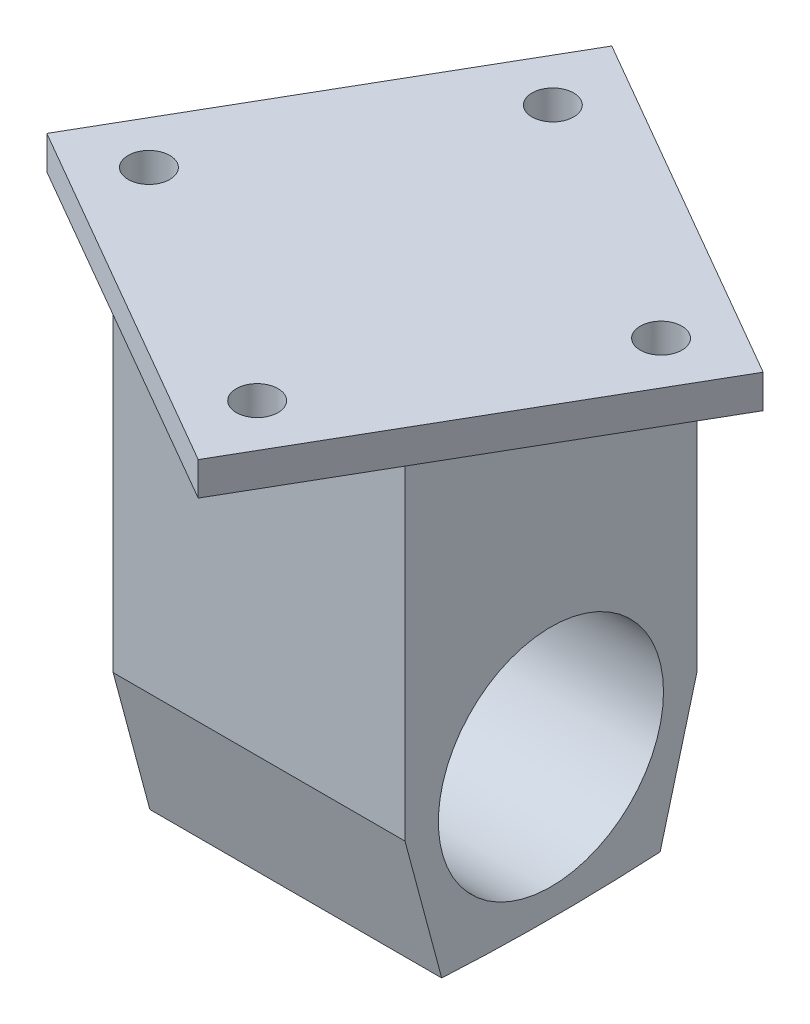
SolidWorks part; units mm, degrees
material "ABS"
ref_plane "Front Plane" through (0, 0, 0) normal (0, 0, 1) x (1, 0, 0)
ref_plane "Top Plane" through (0, 0, 0) normal (0, 1, 0) x (1, 0, 0)
ref_plane "Right Plane" through (0, 0, 0) normal (1, 0, 0) x (0, 0, -1)
sketch "Sketch1" plane through (0, 0, 0) normal (0, 1, 0) x (1, 0, 0)
  line L1 (-22.225, -22.225) -> (22.225, -22.225)
  line L2 (-22.225, -22.225) -> (-22.225, 22.225)
  line L3 (-22.225, 22.225) -> (22.225, 22.225)
  line L4 (22.225, -22.225) -> (22.225, 22.225)
  line L5 (-22.225, -22.225) -> (22.225, 22.225) construction
  line L6 (-22.225, 22.225) -> (22.225, -22.225) construction
  point P0 (0, 0)
extrude "Boss-Extrude1" add sketch "Sketch1" along normal blind 50.292
sketch "Sketch2" plane through (22.225, 0, 0) normal (1, 0, 0) x (0, 0, -1)
  line L0 (-22.225, 0) -> (-16.6371, -20.8543)
  line L1 (22.225, 0) -> (16.6371, -20.8543)
  line L2 (-22.225, 0) -> (22.225, 0)
  line L3 (-22.225, 0) -> (22.225, 0) construction
  arc A1 (16.6371, -20.8543) -> (-16.6371, -20.8543) centre (0, 278.6719) cw
  dimension "D1" = 21.59
  dimension "D2" = 21.59
  dimension "D3" = 75
  dimension "D4" = 75
extrude "Boss-Extrude2" add sketch "Sketch2" against normal up to vertex (44.45 mm away) contours L0 A1 L1 L2 up to point (-22.225, 0, -22.225)
sketch "Sketch3" plane through (22.225, 0, 0) normal (1, 0, 0) x (0, 0, -1)
  circle A0 centre (0, 0) radius 17.145
extrude "Cut-Extrude1" cut sketch "Sketch3" against normal blind 127 contours A0
sketch "Sketch4" plane through (0, 50.292, 0) normal (0, 1, 0) x (1, 0, 0)
  line L0 (-46.8473, -12.5527) -> (46.8473, 12.5527) construction
  line L5 (13.6389, -50.901) -> (-13.6389, 50.901) construction
  line L6 (43.0243, 11.5283) -> (11.5283, -43.0243)
  line L11 (11.5283, -43.0243) -> (-43.0243, -11.5283)
  line L12 (-43.0243, -11.5283) -> (-11.5283, 43.0243)
  line L13 (-11.5283, 43.0243) -> (43.0243, 11.5283)
  line L14 (11.5283, -43.0243) -> (-11.5283, 43.0243) construction
  line L15 (-43.0243, -11.5283) -> (43.0243, 11.5283) construction
  point P1 (0, 0)
  point P4 (0, 0)
  point P11 (0, 0)
  dimension "D1" = 62.992
  dimension "D2" = 62.992
  dimension "D3" = 0
  dimension "D4" = 0
extrude "Boss-Extrude3" add sketch "Sketch4" along normal blind 5.08
sketch "Sketch5" plane through (0, 55.372, 0) normal (0, 1, 0) x (1, 0, 0)
  line L2 (30.7571, 8.2413) -> (43.0243, 11.5283) construction
  line L3 (8.2413, -30.7571) -> (11.5283, -43.0243) construction
  line L4 (-30.7571, -8.2413) -> (-43.0243, -11.5283) construction
  line L5 (-8.2413, 30.7571) -> (-11.5283, 43.0243) construction
  line L6 (-11.5283, 43.0243) -> (-43.0243, -11.5283) construction
  line L7 (43.0243, 11.5283) -> (-11.5283, 43.0243) construction
  line L8 (-43.0243, -11.5283) -> (11.5283, -43.0243) construction
  circle A0 centre (30.7571, 8.2413) radius 3.175
  circle A1 centre (8.2413, -30.7571) radius 3.175
  circle A2 centre (-8.2413, 30.7571) radius 3.175
  circle A3 centre (-30.7571, -8.2413) radius 3.175
  point P2 (0, 0)
  dimension "D2" = 6.35
  dimension "D4" = 6.35
  dimension "D11" = 6.35
  dimension "D12" = 6.35
  dimension "D1" = 12.7
  dimension "D3" = 45
  dimension "D5" = 12.7
  dimension "D6" = 45
  dimension "D7" = 12.7
  dimension "D8" = 45
  dimension "D9" = 12.7
  dimension "D10" = 45
extrude "Cut-Extrude2" cut sketch "Sketch5" against normal through all
